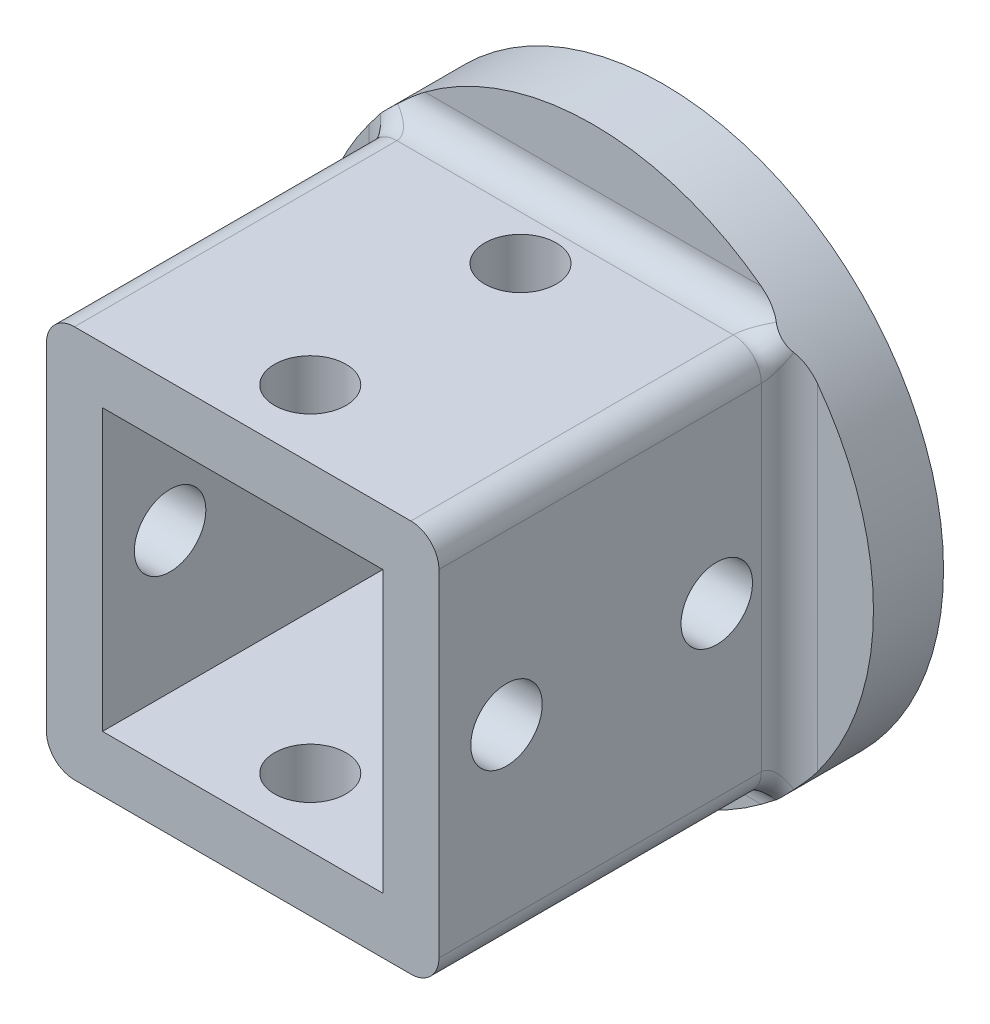
SolidWorks part; units mm, degrees
ref_plane "前视基准面" through (0, 0, 0) normal (0, 0, 1) x (1, 0, 0)
ref_plane "上视基准面" through (0, 0, 0) normal (0, 1, 0) x (1, 0, 0)
ref_plane "右视基准面" through (0, 0, 0) normal (1, 0, 0) x (0, 0, -1)
sketch "草图1" plane through (0, 0, 0) normal (0, 0, 1) x (1, 0, 0)
  circle A0 centre (0, 0) radius 20
  dimension "D1" = 40
extrude "凸台-拉伸1" add sketch "草图1" along normal blind 5
sketch "草图2" plane through (0, 0, 5) normal (0, 0, 1) x (1, 0, 0)
  line L1 (4.95, -4.95) -> (-4.95, -4.95) construction
  line L2 (4.95, -4.95) -> (4.95, 4.95) construction
  line L3 (4.95, 4.95) -> (-4.95, 4.95) construction
  line L4 (-4.95, -4.95) -> (-4.95, 4.95) construction
  line L5 (4.95, -4.95) -> (-4.95, 4.95) construction
  line L6 (4.95, 4.95) -> (-4.95, -4.95) construction
  circle A0 centre (-4.95, 4.95) radius 1.5
  circle A1 centre (4.95, 4.95) radius 1.5
  circle A2 centre (-4.95, -4.95) radius 1.5
  circle A3 centre (4.95, -4.95) radius 1.5
  point P0 (0, 0)
  dimension "D3" = 3
  dimension "D4" = 3
  dimension "D5" = 3
  dimension "D6" = 3
  dimension "D1" = 9.9
  dimension "D2" = 9.9
extrude "切除-拉伸1" cut sketch "草图2" against normal blind 5
sketch "草图4" plane through (0, 0, 5) normal (0, 0, 1) x (1, 0, 0)
  line L5 (-10, 10) -> (10, 10)
  line L23 (-10, 10) -> (-10, -10)
  line L27 (-10, -10) -> (10, -10)
  line L28 (10, 10) -> (10, -10)
  line L33 (-10, 10) -> (10, -10) construction
  line L34 (-10, -10) -> (10, 10) construction
  line L35 (-14, 14) -> (14, 14)
  line L36 (-14, 14) -> (-14, -14)
  line L37 (-14, -14) -> (14, -14)
  line L38 (14, 14) -> (14, -14)
  line L39 (-14, 14) -> (14, -14) construction
  line L40 (-14, -14) -> (14, 14) construction
  point P0 (0, 0)
  point P5 (0, 0)
  dimension "D1" = 20
  dimension "D2" = 28
extrude "凸台-拉伸3" add sketch "草图4" along normal blind 25 contours L38 L35 L36 L37 L5 L28 L27 L23 region at (0, 13.604, 5)
sketch "草图5" plane through (-14, 0, 0) normal (-1, 0, 0) x (0, 0, 1)
  line L0 (30.0014, 0) -> (0, 0) construction
  line L2 (0, 20) -> (0, -20) construction
  circle A0 centre (10.1786, 0) radius 2.55
  circle A1 centre (25.1786, 0) radius 2.55
  circle A2 centre (40.1786, 0) radius 2.55
  point P2 (30, -0.1421)
  point P3 (0, 0)
  point P4 (0, 0)
  point P7 (0, 0)
  point P8 (0, 0)
  point P13 (0, 0)
  point P16 (0, 0)
  point P17 (0, 0)
  point P18 (0, 0)
  point P19 (0, 0)
  point P20 (0, 0)
  point P21 (0, 0)
  dimension "D1" = 3
  dimension "D2" = 5.1
extrude "切除-拉伸2" cut sketch "草图5" against normal through all
sketch "草图6" plane through (0, 14, 0) normal (0, 1, 0) x (1, 0, 0)
  line L0 (0, -5) -> (0, -10.18) construction
  line L2 (-14, -5) -> (14, -5) construction
  circle A0 centre (0, -10.18) radius 2.55
  circle A1 centre (0, -25.18) radius 2.55
  circle A2 centre (0, -40.18) radius 2.55
  point P2 (0, -5)
  point P5 (0, 0)
  dimension "D2" = 5.1
  dimension "D3" = 3
extrude "切除-拉伸3" cut sketch "草图6" against normal through all
fillet "圆角1" radius 2 4 edges at (14, 0, 5) (0, 14, 5) (-14, 0, 5) (0, -14, 5)
fillet "圆角2" radius 2 8 edges at (14.0359, 14.0359, 6.623) (14.0359, -14.0359, 6.623) (-14.0359, -14.0359, 6.623) (-14.0359, 14.0359, 6.623) (14, 14, 18.5) (14, -14, 18.5) (-14, -14, 18.5) (-14, 14, 18.5)
